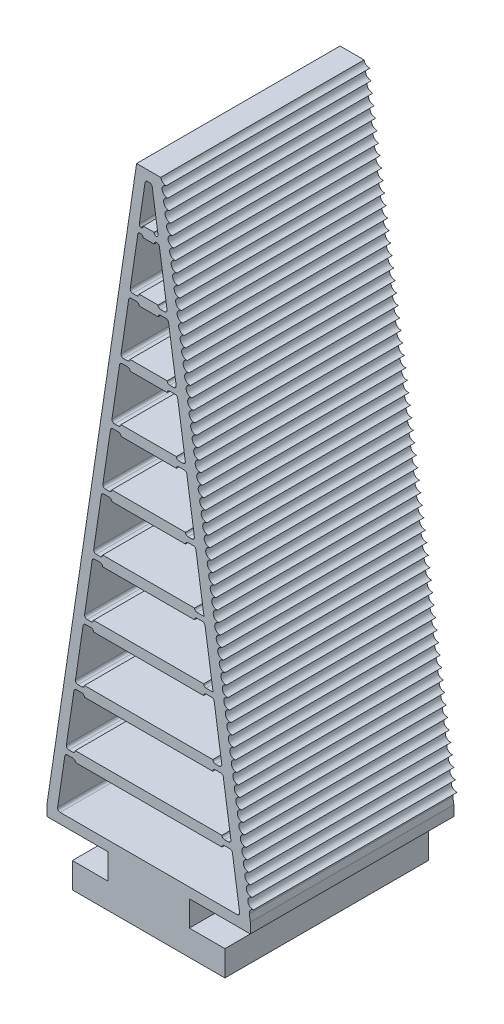
SolidWorks part; units mm, degrees
ref_plane "Front Plane" through (0, 0, 0) normal (0, 0, 1) x (1, 0, 0)
ref_plane "Top Plane" through (0, 0, 0) normal (0, 1, 0) x (1, 0, 0)
ref_plane "Right Plane" through (0, 0, 0) normal (1, 0, 0) x (0, 0, -1)
sketch "Sketch1" plane through (0, 0, 0) normal (0, 0, 1) x (1, 0, 0)
  line L0 (-15, 0) -> (15, 0)
  line L1 (15, 0) -> (15, 5)
  line L2 (15, 5) -> (8, 5)
  line L3 (8, 5) -> (8, 10)
  line L4 (8, 10) -> (20, 10)
  line L5 (20, 10) -> (20, 12)
  line L6 (20, 12) -> (2.3648, 130)
  line L7 (2.3648, 130) -> (-2.3648, 130)
  line L8 (-2.3648, 130) -> (-20, 12)
  line L9 (-20, 12) -> (-20, 10)
  line L10 (-20, 10) -> (-8, 10)
  line L11 (-8, 10) -> (-8, 5)
  line L12 (-8, 5) -> (-15, 5)
  line L13 (-15, 5) -> (-15, 0)
  point P17 (0, 130)
  point P19 (0, 0)
  dimension "D1" = 20
  dimension "D2" = 15
  dimension "D3" = 5
  dimension "D4" = 10
  dimension "D5" = 2
  dimension "D6" = 17
  dimension "D7" = 120
  dimension "D8" = 8
extrude "Boss-Extrude1" add sketch "Sketch1" along normal blind 40 contours L8 L9 L10 L11 L12 L13 L0 L1 L2 L3 L4 L5 L6 L7
sketch "Sketch2" plane through (0, 0, 40) normal (0, 0, 1) x (1, 0, 0)
  line L0 (-17.9778, 12) -> (17.9778, 12)
  line L1 (17.9778, 12) -> (16.4086, 22.5)
  line L3 (-16.4086, 22.5) -> (-17.9778, 12)
  line L4 (-2.3648, 130) -> (-20, 12) construction
  line L5 (-20, 10) -> (-8, 10) construction
  line L6 (20, 12) -> (2.3648, 130) construction
  line L8 (-16.4086, 22.5) -> (-14.4086, 22.5)
  line L9 (-14.4086, 22.5) -> (-14.4086, 22)
  line L10 (-14.4086, 22) -> (14.4086, 22)
  line L11 (14.4086, 22) -> (14.4086, 22.5)
  line L12 (14.4086, 22.5) -> (16.4086, 22.5)
  dimension "D1" = 2
  dimension "D2" = 2
  dimension "D3" = 2
  dimension "D4" = 2
  dimension "D5" = 0.5
  dimension "D6" = 10
extrude "Cut-Extrude1" cut sketch "Sketch2" against normal through all
sketch "Sketch3" plane through (0, 0, 40) normal (0, 0, 1) x (1, 0, 0)
  line L0 (-16.2591, 23.5) -> (-14.4086, 23.5)
  line L1 (-14.4086, 23.5) -> (-14.4086, 24)
  line L2 (-14.4086, 24) -> (14.4086, 24)
  line L3 (14.4086, 24) -> (14.4086, 23.5)
  line L4 (14.4086, 23.5) -> (16.2591, 23.5)
  line L5 (16.2591, 23.5) -> (14.6151, 34.5)
  line L6 (14.6151, 34.5) -> (12.6151, 34.5)
  line L7 (12.6151, 34.5) -> (12.6151, 34)
  line L8 (12.6151, 34) -> (-12.6151, 34)
  line L9 (-12.6151, 34) -> (-12.6151, 34.5)
  line L10 (-14.6151, 34.5) -> (-16.2591, 23.5)
  line L11 (-12.6151, 34.5) -> (-14.6151, 34.5)
  line L13 (-16.4086, 22.5) -> (-17.9778, 12) construction
  line L15 (17.9778, 12) -> (16.4086, 22.5) construction
  line L16 (-14.4086, 22.5) -> (-16.4086, 22.5) construction
  line L18 (-14.4086, 22) -> (-14.4086, 22.5) construction
  line L19 (14.4086, 22.5) -> (14.4086, 22) construction
  dimension "D1" = 1
  dimension "D2" = 0.5
  dimension "D3" = 10
  dimension "D4" = 0.5
  dimension "D5" = 2
extrude "Cut-Extrude2" cut sketch "Sketch3" against normal through all
sketch "Sketch4" plane through (0, 0, 40) normal (0, 0, 1) x (1, 0, 0)
  line L0 (-14.4657, 35.5) -> (-12.6151, 35.5)
  line L1 (-12.6151, 35.5) -> (-12.6151, 36)
  line L2 (-12.6151, 36) -> (12.6151, 36)
  line L3 (12.6151, 36) -> (12.6151, 35.5)
  line L4 (12.6151, 35.5) -> (14.4657, 35.5)
  line L5 (14.4657, 35.5) -> (12.8217, 46.5)
  line L6 (12.8217, 46.5) -> (10.8217, 46.5)
  line L7 (10.8217, 46.5) -> (10.8217, 46)
  line L8 (10.8217, 46) -> (-10.8217, 46)
  line L9 (-10.8217, 46) -> (-10.8217, 46.5)
  line L10 (-10.8217, 46.5) -> (-12.8217, 46.5)
  line L11 (-12.8217, 46.5) -> (-14.4657, 35.5)
  line L12 (-14.6151, 34.5) -> (-16.2591, 23.5) construction
  line L13 (16.2591, 23.5) -> (14.6151, 34.5) construction
  line L14 (-12.6151, 34.5) -> (-14.6151, 34.5) construction
  line L16 (-12.6151, 34) -> (-12.6151, 34.5) construction
  dimension "D1" = 10
  dimension "D2" = 0.5
  dimension "D3" = 0.5
  dimension "D4" = 1
  dimension "D5" = 2
extrude "Cut-Extrude3" cut sketch "Sketch4" against normal through all
sketch "Sketch5" plane through (0, 0, 40) normal (0, 0, 1) x (1, 0, 0)
  line L0 (-12.6723, 47.5) -> (-10.8217, 47.5)
  line L1 (-10.8217, 47.5) -> (-10.8217, 48)
  line L2 (-10.8217, 48) -> (10.8217, 48)
  line L3 (10.8217, 48) -> (10.8217, 47.5)
  line L4 (10.8217, 47.5) -> (12.6723, 47.5)
  line L5 (12.6723, 47.5) -> (11.0283, 58.5)
  line L6 (11.0283, 58.5) -> (9.0283, 58.5)
  line L7 (9.0283, 58.5) -> (9.0283, 58)
  line L8 (9.0283, 58) -> (-9.0283, 58)
  line L9 (-9.0283, 58) -> (-9.0283, 58.5)
  line L10 (-9.0283, 58.5) -> (-11.0283, 58.5)
  line L11 (-11.0283, 58.5) -> (-12.6723, 47.5)
  line L12 (-12.8217, 46.5) -> (-14.4657, 35.5) construction
  line L14 (14.4657, 35.5) -> (12.8217, 46.5) construction
  line L15 (-10.8217, 46.5) -> (-12.8217, 46.5) construction
  line L16 (-10.8217, 46) -> (-10.8217, 46.5) construction
  dimension "D1" = 10
  dimension "D2" = 2
  dimension "D3" = 0.5
  dimension "D4" = 0.5
  dimension "D5" = 1
extrude "Cut-Extrude4" cut sketch "Sketch5" against normal through all
sketch "Sketch6" plane through (0, 0, 40) normal (0, 0, 1) x (1, 0, 0)
  line L0 (-10.8789, 59.5) -> (-9.0283, 59.5)
  line L1 (-9.0283, 59.5) -> (-9.0283, 60)
  line L2 (-9.0283, 60) -> (9.0283, 60)
  line L3 (9.0283, 60) -> (9.0283, 59.5)
  line L4 (9.0283, 59.5) -> (10.8789, 59.5)
  line L5 (10.8789, 59.5) -> (9.2349, 70.5)
  line L6 (9.2349, 70.5) -> (7.2349, 70.5)
  line L7 (7.2349, 70.5) -> (7.2349, 70)
  line L8 (7.2349, 70) -> (-7.2349, 70)
  line L9 (-7.2349, 70) -> (-7.2349, 70.5)
  line L10 (-7.2349, 70.5) -> (-9.2349, 70.5)
  line L11 (-9.2349, 70.5) -> (-10.8789, 59.5)
  line L12 (-11.0283, 58.5) -> (-12.6723, 47.5) construction
  line L13 (12.6723, 47.5) -> (11.0283, 58.5) construction
  line L14 (-9.0283, 58) -> (-9.0283, 58.5) construction
  line L15 (9.0283, 58.5) -> (9.0283, 58) construction
  line L16 (9.0283, 58) -> (-9.0283, 58) construction
  dimension "D1" = 10
  dimension "D2" = 0.5
  dimension "D3" = 2
  dimension "D4" = 0.5
  dimension "D5" = 2
extrude "Cut-Extrude5" cut sketch "Sketch6" against normal through all
sketch "Sketch7" plane through (0, 0, 40) normal (0, 0, 1) x (1, 0, 0)
  line L0 (-9.0855, 71.5) -> (-7.2349, 71.5)
  line L1 (-7.2349, 71.5) -> (-7.2349, 72)
  line L2 (-7.2349, 72) -> (7.2349, 72)
  line L3 (7.2349, 72) -> (7.2349, 71.5)
  line L4 (7.2349, 71.5) -> (9.0855, 71.5)
  line L5 (9.0855, 71.5) -> (7.4415, 82.5)
  line L6 (7.4415, 82.5) -> (5.4415, 82.5)
  line L7 (5.4415, 82.5) -> (5.4415, 82)
  line L8 (5.4415, 82) -> (-5.4415, 82)
  line L9 (-5.4415, 82) -> (-5.4415, 82.5)
  line L10 (-5.4415, 82.5) -> (-7.4415, 82.5)
  line L11 (-7.4415, 82.5) -> (-9.0855, 71.5)
  line L13 (-7.2349, 70) -> (-7.2349, 70.5) construction
  line L14 (7.2349, 70.5) -> (7.2349, 70) construction
  line L15 (-9.2349, 70.5) -> (-10.8789, 59.5) construction
  line L16 (10.8789, 59.5) -> (9.2349, 70.5) construction
  line L17 (-7.2349, 70.5) -> (-9.2349, 70.5) construction
  dimension "D1" = 2
  dimension "D2" = 10
  dimension "D3" = 0.5
  dimension "D4" = 0.5
  dimension "D5" = 1
extrude "Cut-Extrude6" cut sketch "Sketch7" against normal through all
sketch "Sketch8" plane through (0, 0, 40) normal (0, 0, 1) x (1, 0, 0)
  line L0 (-7.292, 83.5) -> (-5.4415, 83.5)
  line L1 (-5.4415, 83.5) -> (-5.4415, 84)
  line L2 (-5.4415, 84) -> (5.4415, 84)
  line L3 (5.4415, 84) -> (5.4415, 83.5)
  line L4 (5.4415, 83.5) -> (7.292, 83.5)
  line L5 (7.292, 83.5) -> (5.6481, 94.5)
  line L6 (5.6481, 94.5) -> (3.6481, 94.5)
  line L7 (3.6481, 94.5) -> (3.6481, 94)
  line L8 (3.6481, 94) -> (-3.6481, 94)
  line L9 (-3.6481, 94) -> (-3.6481, 94.5)
  line L10 (-3.6481, 94.5) -> (-5.6481, 94.5)
  line L11 (-5.6481, 94.5) -> (-7.292, 83.5)
  line L12 (-7.4415, 82.5) -> (-9.0855, 71.5) construction
  line L13 (9.0855, 71.5) -> (7.4415, 82.5) construction
  line L14 (-5.4415, 82) -> (-5.4415, 82.5) construction
  line L15 (5.4415, 82) -> (-5.4415, 82) construction
  line L16 (-5.4415, 82.5) -> (-7.4415, 82.5) construction
  dimension "D1" = 2
  dimension "D2" = 10
  dimension "D3" = 2
  dimension "D4" = 1
  dimension "D5" = 0.5
extrude "Cut-Extrude7" cut sketch "Sketch8" against normal through all contours L2 L3 L4 L5 L6 L7 L8 L9 L10 L11 L0 L1
sketch "Sketch10" plane through (0, 0, 40) normal (0, 0, 1) x (1, 0, 0)
  line L0 (-5.4986, 95.5) -> (-3.6481, 95.5)
  line L1 (-3.6481, 95.5) -> (-3.6481, 96)
  line L2 (-3.6481, 96) -> (3.6481, 96)
  line L3 (3.6481, 96) -> (3.6481, 95.5)
  line L4 (3.6481, 95.5) -> (5.4986, 95.5)
  line L5 (5.4986, 95.5) -> (3.8547, 106.5)
  line L6 (3.8547, 106.5) -> (1.8547, 106.5)
  line L7 (1.8547, 106.5) -> (1.8547, 106)
  line L8 (1.8547, 106) -> (-1.8547, 106)
  line L9 (-1.8547, 106) -> (-1.8547, 106.5)
  line L10 (-1.8547, 106.5) -> (-3.8547, 106.5)
  line L11 (-3.8547, 106.5) -> (-5.4986, 95.5)
  line L12 (-5.6481, 94.5) -> (-7.292, 83.5) construction
  line L13 (7.292, 83.5) -> (5.6481, 94.5) construction
  line L14 (-3.6481, 94) -> (-3.6481, 94.5) construction
  line L16 (-3.6481, 94.5) -> (-5.6481, 94.5) construction
  line L17 (3.6481, 94) -> (-3.6481, 94) construction
  dimension "D1" = 1
  dimension "D2" = 2
  dimension "D3" = 0.5
  dimension "D4" = 2
  dimension "D5" = 10
extrude "Cut-Extrude8" cut sketch "Sketch10" against normal through all
sketch "Sketch11" plane through (0, 0, 40) normal (0, 0, 1) x (1, 0, 0)
  line L0 (-3.7052, 107.5) -> (-1.8547, 107.5)
  line L1 (-1.8547, 107.5) -> (-1.8547, 108)
  line L2 (-1.8547, 108) -> (1.8547, 108)
  line L3 (1.8547, 108) -> (1.8547, 107.5)
  line L4 (1.8547, 107.5) -> (3.7052, 107.5)
  line L5 (3.7052, 107.5) -> (2.0613, 118.5)
  line L6 (2.0613, 118.5) -> (1.0613, 118.5)
  line L7 (1.0613, 118.5) -> (1.0613, 118)
  line L8 (1.0613, 118) -> (-1.0613, 118)
  line L9 (-1.0613, 118) -> (-1.0613, 118.5)
  line L10 (-1.0613, 118.5) -> (-2.0613, 118.5)
  line L11 (-2.0613, 118.5) -> (-3.7052, 107.5)
  line L12 (-3.8547, 106.5) -> (-5.4986, 95.5) construction
  line L14 (5.4986, 95.5) -> (3.8547, 106.5) construction
  line L15 (-1.8547, 106) -> (-1.8547, 106.5) construction
  line L17 (1.8547, 106.5) -> (1.8547, 106) construction
  line L18 (1.8547, 106) -> (-1.8547, 106) construction
  dimension "D1" = 0.5
  dimension "D2" = 1
  dimension "D3" = 10
  dimension "D4" = 0.5
  dimension "D5" = 2
extrude "Cut-Extrude9" cut sketch "Sketch11" against normal through all
sketch "Sketch12" plane through (0, 0, 40) normal (0, 0, 1) x (1, 0, 0)
  line L0 (-1.9118, 119.5) -> (-1.0613, 119.5)
  line L1 (-1.0613, 119.5) -> (-1.0613, 120)
  line L2 (-1.0613, 120) -> (1.0613, 120)
  line L3 (1.0613, 120) -> (1.0613, 119.5)
  line L4 (1.0613, 119.5) -> (1.9118, 119.5)
  line L5 (1.9118, 119.5) -> (0.6415, 128)
  line L6 (0.6415, 128) -> (-0.6415, 128)
  line L7 (-0.6415, 128) -> (-1.9118, 119.5)
  line L8 (-2.0613, 118.5) -> (-3.7052, 107.5) construction
  line L9 (3.7052, 107.5) -> (2.0613, 118.5) construction
  line L10 (-1.0613, 118) -> (-1.0613, 118.5) construction
  line L11 (1.0613, 118) -> (-1.0613, 118) construction
  line L12 (-1.0613, 118.5) -> (-2.0613, 118.5) construction
  line L13 (2.3648, 130) -> (-2.3648, 130) construction
  dimension "D1" = 2
  dimension "D2" = 1
  dimension "D3" = 2
extrude "Cut-Extrude10" cut sketch "Sketch12" against normal through all contours L7 L0 L1 L2 L3 L4 L5 L6
fillet "Fillet1" radius 0.5 36 edges at (-1.0613, 119.5, 20) (-1.8547, 107.5, 20) (-1.0613, 118.5, 20) (-1.8547, 106.5, 20) (1.0613, 119.5, 20) (1.0613, 118.5, 20) (1.8547, 106.5, 20) (3.6481, 94.5, 20) (-3.6481, 94.5, 20) (-5.4415, 82.5, 20) (-3.6481, 95.5, 20) (-5.4415, 83.5, 20) (-7.2349, 71.5, 20) (-9.0283, 59.5, 20) (1.8547, 107.5, 20) (3.6481, 95.5, 20) (5.4415, 83.5, 20) (7.2349, 71.5, 20) (9.0283, 59.5, 20) (10.8217, 47.5, 20) (5.4415, 82.5, 20) (7.2349, 70.5, 20) (9.0283, 58.5, 20) (10.8217, 46.5, 20) (-7.2349, 70.5, 20) (-9.0283, 58.5, 20) (-10.8217, 46.5, 20) (-10.8217, 47.5, 20) (-12.6151, 35.5, 20) (12.6151, 35.5, 20) (12.6151, 34.5, 20) (-12.6151, 34.5, 20) (-14.4086, 22.5, 20) (-14.4086, 23.5, 20) (14.4086, 22.5, 20) (14.4086, 23.5, 20)
sketch "Sketch13" plane through (0, 0, 40) normal (0, 0, 1) x (1, 0, 0)
  line L0 (2.3648, 130) -> (19.8063, 13.2961) construction
  line L1 (20.6475, 14.433) -> (3.3538, 130.1478) construction
  line L2 (3.3538, 130.1478) -> (2.3648, 130) construction
  line L4 (20, 12) -> (2.3648, 130) construction
  line L5 (2.3648, 130) -> (0.3426, 130)
  line L6 (2.3648, 130) -> (-2.3648, 130) construction
  line L7 (0.3426, 130) -> (17.8283, 13.0005)
  line L8 (17.9778, 12) -> (16.4086, 22.5) construction
  line L9 (17.8283, 13.0005) -> (19.8063, 13.2961)
  arc A0 (2.3648, 130) -> (3.5016, 129.1588) centre (3.3538, 130.1478) ccw
  arc A1 (3.5016, 129.1588) -> (3.7972, 127.1808) centre (3.6494, 128.1698) ccw
  arc A2 (3.7972, 127.1808) -> (4.0928, 125.2027) centre (3.945, 126.1917) ccw
  arc A3 (4.0928, 125.2027) -> (4.3885, 123.2247) centre (4.2407, 124.2137) ccw
  arc A4 (4.3885, 123.2247) -> (4.6841, 121.2467) centre (4.5363, 122.2357) ccw
  arc A5 (4.6841, 121.2467) -> (4.9797, 119.2686) centre (4.8319, 120.2577) ccw
  arc A6 (4.9797, 119.2686) -> (5.2753, 117.2906) centre (5.1275, 118.2796) ccw
  arc A7 (5.2753, 117.2906) -> (5.5709, 115.3126) centre (5.4231, 116.3016) ccw
  arc A8 (5.5709, 115.3126) -> (5.8666, 113.3345) centre (5.7187, 114.3236) ccw
  arc A9 (5.8666, 113.3345) -> (6.1622, 111.3565) centre (6.0144, 112.3455) ccw
  arc A10 (6.1622, 111.3565) -> (6.4578, 109.3785) centre (6.31, 110.3675) ccw
  arc A11 (6.4578, 109.3785) -> (6.7534, 107.4004) centre (6.6056, 108.3895) ccw
  arc A12 (6.7534, 107.4004) -> (7.049, 105.4224) centre (6.9012, 106.4114) ccw
  arc A13 (7.049, 105.4224) -> (7.3447, 103.4444) centre (7.1968, 104.4334) ccw
  arc A14 (7.3447, 103.4444) -> (7.6403, 101.4663) centre (7.4925, 102.4554) ccw
  arc A15 (7.6403, 101.4663) -> (7.9359, 99.4883) centre (7.7881, 100.4773) ccw
  arc A16 (7.9359, 99.4883) -> (8.2315, 97.5103) centre (8.0837, 98.4993) ccw
  arc A17 (8.2315, 97.5103) -> (8.5271, 95.5323) centre (8.3793, 96.5213) ccw
  arc A18 (8.5271, 95.5323) -> (8.8227, 93.5542) centre (8.6749, 94.5432) ccw
  arc A19 (8.8227, 93.5542) -> (9.1184, 91.5762) centre (8.9706, 92.5652) ccw
  arc A20 (9.1184, 91.5762) -> (9.414, 89.5982) centre (9.2662, 90.5872) ccw
  arc A21 (9.414, 89.5982) -> (9.7096, 87.6201) centre (9.5618, 88.6091) ccw
  arc A22 (9.7096, 87.6201) -> (10.0052, 85.6421) centre (9.8574, 86.6311) ccw
  arc A23 (10.0052, 85.6421) -> (10.3008, 83.6641) centre (10.153, 84.6531) ccw
  arc A24 (10.3008, 83.6641) -> (10.5965, 81.686) centre (10.4486, 82.675) ccw
  arc A25 (10.5965, 81.686) -> (10.8921, 79.708) centre (10.7443, 80.697) ccw
  arc A26 (10.8921, 79.708) -> (11.1877, 77.73) centre (11.0399, 78.719) ccw
  arc A27 (11.1877, 77.73) -> (11.4833, 75.7519) centre (11.3355, 76.741) ccw
  arc A28 (11.4833, 75.7519) -> (11.7789, 73.7739) centre (11.6311, 74.7629) ccw
  arc A29 (11.7789, 73.7739) -> (12.0746, 71.7959) centre (11.9267, 72.7849) ccw
  arc A30 (12.0746, 71.7959) -> (12.3702, 69.8178) centre (12.2224, 70.8069) ccw
  arc A31 (12.3702, 69.8178) -> (12.6658, 67.8398) centre (12.518, 68.8288) ccw
  arc A32 (12.6658, 67.8398) -> (12.9614, 65.8618) centre (12.8136, 66.8508) ccw
  arc A33 (12.9614, 65.8618) -> (13.257, 63.8837) centre (13.1092, 64.8728) ccw
  arc A34 (13.257, 63.8837) -> (13.5526, 61.9057) centre (13.4048, 62.8947) ccw
  arc A35 (13.5526, 61.9057) -> (13.8483, 59.9277) centre (13.7005, 60.9167) ccw
  arc A36 (13.8483, 59.9277) -> (14.1439, 57.9497) centre (13.9961, 58.9387) ccw
  arc A37 (14.1439, 57.9497) -> (14.4395, 55.9716) centre (14.2917, 56.9606) ccw
  arc A38 (14.4395, 55.9716) -> (14.7351, 53.9936) centre (14.5873, 54.9826) ccw
  arc A39 (14.7351, 53.9936) -> (15.0307, 52.0156) centre (14.8829, 53.0046) ccw
  arc A40 (15.0307, 52.0156) -> (15.3264, 50.0375) centre (15.1786, 51.0265) ccw
  arc A41 (15.3264, 50.0375) -> (15.622, 48.0595) centre (15.4742, 49.0485) ccw
  arc A42 (15.622, 48.0595) -> (15.9176, 46.0815) centre (15.7698, 47.0705) ccw
  arc A43 (15.9176, 46.0815) -> (16.2132, 44.1034) centre (16.0654, 45.0924) ccw
  arc A44 (16.2132, 44.1034) -> (16.5088, 42.1254) centre (16.361, 43.1144) ccw
  arc A45 (16.5088, 42.1254) -> (16.8045, 40.1474) centre (16.6566, 41.1364) ccw
  arc A46 (16.8045, 40.1474) -> (17.1001, 38.1693) centre (16.9523, 39.1583) ccw
  arc A47 (17.1001, 38.1693) -> (17.3957, 36.1913) centre (17.2479, 37.1803) ccw
  arc A48 (17.3957, 36.1913) -> (17.6913, 34.2133) centre (17.5435, 35.2023) ccw
  arc A49 (17.6913, 34.2133) -> (17.9869, 32.2352) centre (17.8391, 33.2243) ccw
  arc A50 (17.9869, 32.2352) -> (18.2825, 30.2572) centre (18.1347, 31.2462) ccw
  arc A51 (18.2825, 30.2572) -> (18.5782, 28.2792) centre (18.4304, 29.2682) ccw
  arc A52 (18.5782, 28.2792) -> (18.8738, 26.3011) centre (18.726, 27.2902) ccw
  arc A53 (18.8738, 26.3011) -> (19.1694, 24.3231) centre (19.0216, 25.3121) ccw
  arc A54 (19.1694, 24.3231) -> (19.465, 22.3451) centre (19.3172, 23.3341) ccw
  arc A55 (19.465, 22.3451) -> (19.7606, 20.367) centre (19.6128, 21.3561) ccw
  arc A56 (19.7606, 20.367) -> (20.0563, 18.389) centre (19.9085, 19.378) ccw
  arc A57 (20.0563, 18.389) -> (20.3519, 16.411) centre (20.2041, 17.4) ccw
  arc A58 (20.3519, 16.411) -> (20.6475, 14.433) centre (20.4997, 15.422) ccw
  arc A59 (20.6475, 14.433) -> (19.8063, 13.2961) centre (20.7953, 13.4439) ccw
  dimension "D1" = 1
extrude "Boss-Extrude2" add sketch "Sketch13" against normal up to surface (40 mm away) contours A1 A2 A3 A4 A5 A6 A7 A8 A9 A10 A11 A12 A13 A14 A15 A16 A17 A18 A19 A20 A21 A22 A23 A24 A25 A26 A27 A28 A29 A30 A31 A32 A33 A34 A35 A36 A37 A38 A39 A40 A41 A42 A43 A44 A45 A46 A47 A48 A49 A50 A51 A52 A53 A54 A55 A56 A57 A58 A59 L9 L7 L5 A0 up to face at (0, 121.7241, 0)
fillet "Fillet2" radius 0.5 38 edges at (17.9778, 12, 20) (-17.9778, 12, 20) (0.6415, 128, 20) (-0.6415, 128, 20) (1.9118, 119.5, 20) (-1.9118, 119.5, 20) (-2.0613, 118.5, 20) (2.0613, 118.5, 20) (-3.7052, 107.5, 20) (-3.8547, 106.5, 20) (3.8547, 106.5, 20) (3.7052, 107.5, 20) (5.4986, 95.5, 20) (-5.4986, 95.5, 20) (-5.6481, 94.5, 20) (5.6481, 94.5, 20) (7.4415, 82.5, 20) (7.292, 83.5, 20) (9.0855, 71.5, 20) (-7.292, 83.5, 20) (-9.0855, 71.5, 20) (-10.8789, 59.5, 20) (-12.6723, 47.5, 20) (-7.4415, 82.5, 20) (-9.2349, 70.5, 20) (-11.0283, 58.5, 20) (9.2349, 70.5, 20) (11.0283, 58.5, 20) (12.8217, 46.5, 20) (14.6151, 34.5, 20) (14.4657, 35.5, 20) (-14.4657, 35.5, 20) (-16.2591, 23.5, 20) (-12.8217, 46.5, 20) (-14.6151, 34.5, 20) (-16.4086, 22.5, 20) (16.2591, 23.5, 20) (16.4086, 22.5, 20)
